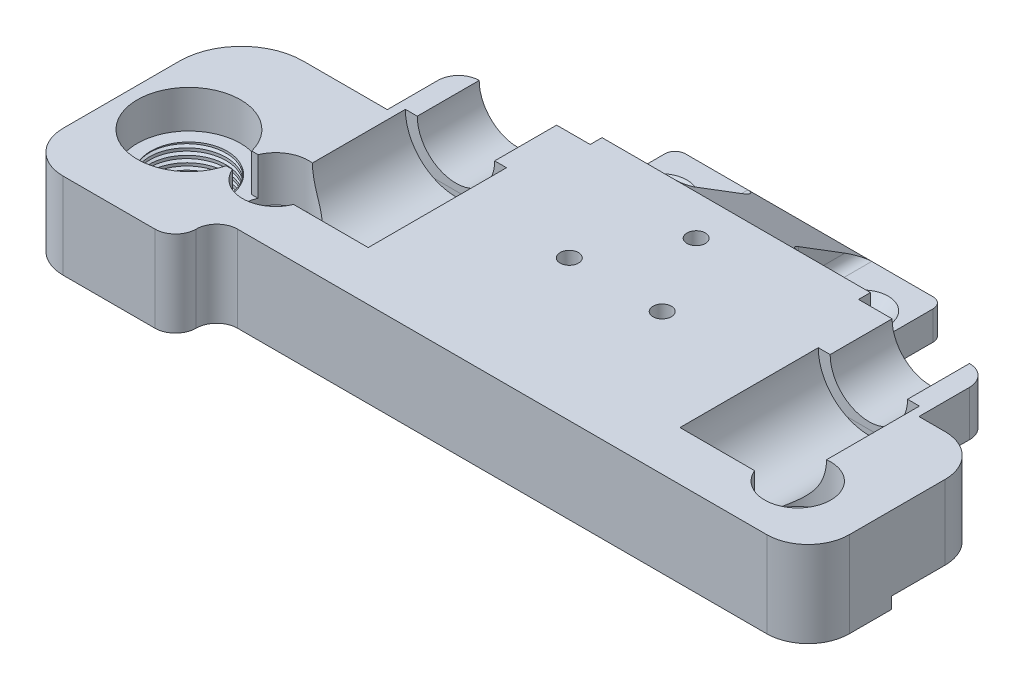
SolidWorks part; units mm, degrees
material "ABS"
ref_plane "Front Plane" through (0, 0, 0) normal (0, 0, 1) x (1, 0, 0)
ref_plane "Top Plane" through (0, 0, 0) normal (0, 1, 0) x (1, 0, 0)
ref_plane "Right Plane" through (0, 0, 0) normal (1, 0, 0) x (0, 0, -1)
sketch "Sketch1" plane through (0, 0, 0) normal (0, 1, 0) x (1, 0, 0)
  line L0 (-0.0671, 38.0105) -> (-0.0671, -29.1298) construction
  line L1 (16.4429, 34.3516) -> (-16.5771, 34.3516)
  line L2 (-41.0754, 15.1359) -> (-16.5771, 15.1359)
  line L3 (-16.5771, 15.1359) -> (-16.5771, 34.3516)
  line L4 (-41.0754, 15.1359) -> (-41.0754, -6.8091)
  line L5 (40.9412, 15.1359) -> (40.9412, -6.8091)
  line L6 (40.9412, 15.1359) -> (16.4429, 15.1359)
  line L7 (16.4429, 15.1359) -> (16.4429, 34.3516)
  line L10 (-41.0754, -6.8091) -> (40.9412, -6.8091)
  circle A0 centre (-12.4496, 28.5096) radius 1.4224
  circle A2 centre (-32.1854, 0.8109) radius 1.9304
  circle A3 centre (32.0512, 0.8109) radius 1.9304
  circle A5 centre (12.3154, 28.5096) radius 1.4224
  point P17 (-0.0671, 34.3516)
  point P20 (-16.5771, 34.3516)
  dimension "D1" = 2.8448
  dimension "D2" = 33.02
  dimension "D3" = 3.8608
  dimension "D6" = 34.0106
  dimension "D7" = 24.765
  dimension "D8" = 64.2366
  dimension "D12" = 5.842
  dimension "D13" = 8.89
  dimension "D14" = 7.62
extrude "Boss-Extrude1" add sketch "Sketch1" along normal blind 3.556
sketch "Sketch3" plane through (0, 0, 0) normal (0, -1, 0) x (1, 0, 0)
  line L0 (40.9412, 6.8091) -> (40.9412, -15.1359) construction
  line L1 (-41.0754, 6.8091) -> (40.9412, 6.8091)
  line L2 (-41.0754, 6.8091) -> (-41.0754, -3.4667)
  line L3 (-41.0754, -3.4667) -> (40.9412, -3.4667)
  line L4 (40.9412, 6.8091) -> (40.9412, -3.4667)
  circle A0 centre (32.0512, -0.8109) radius 1.9304
  circle A1 centre (-32.1854, -0.8109) radius 1.9304
  dimension "D2" = 3.8608
  dimension "D3" = 3.8608
extrude "Boss-Extrude2" add sketch "Sketch3" along normal blind 1.9304
hole_wizard "CSK for M4 Flat Head Machine Screw1" positions "Sketch19" profile "Sketch18" countersink size "M4" standard "ANSI Metric" end condition through all
sketch "Sketch19" plane through (0, 3.556, 0) normal (0, 1, 0) x (1, 0, 0)
  point P0 (-32.1854, 0.8109)
  point P3 (32.0512, 0.8109)
sketch "Sketch18" plane through (-32.1854, 3.556, -0.8109) normal (1, 0, 0) x (0, 0, 1)
  line L0 (0, 0) -> (0, 5.4864)
  line L1 (0, 5.4864) -> (2.25, 5.4864)
  line L2 (2.25, 5.4864) -> (2.25, 1.814)
  line L3 (2.25, 1.814) -> (4.064, 0)
  line L5 (4.064, 0) -> (0, 0)
  line L6 (-2.25, 1.814) -> (-4.064, 0) construction
  line L11 (0, -6.35) -> (0, 107.95) construction
  dimension "Thru Hole Dia." = 4.5
  dimension "Thru Hole Depth" = 5.4864
  dimension "Near C'Sink Dia." = 8.128
  dimension "Near C'Sink Angle" = 90
hole_wizard "CSK for M3 Flat Head Machine Screw2" positions "Sketch22" profile "Sketch21" countersink size "M3" standard "ANSI Metric" end condition through all
sketch "Sketch22" plane through (0, 3.556, 0) normal (0, 1, 0) x (1, 0, 0)
  point P0 (-12.4496, 28.5096)
  point P3 (12.3154, 28.5096)
sketch "Sketch21" plane through (-12.4496, 3.556, -28.5096) normal (1, 0, 0) x (0, 0, 1)
  line L0 (0, 0) -> (0, 5.4864)
  line L1 (0, 5.4864) -> (1.7, 5.4864)
  line L2 (1.7, 5.4864) -> (1.7, 1.45)
  line L3 (1.7, 1.45) -> (3.15, 0)
  line L5 (3.15, 0) -> (0, 0)
  line L6 (-1.7, 1.45) -> (-3.15, 0) construction
  line L11 (0, -6.35) -> (0, 107.95) construction
  dimension "Thru Hole Dia." = 3.4
  dimension "Thru Hole Depth" = 5.4864
  dimension "Near C'Sink Dia." = 6.3
  dimension "Near C'Sink Angle" = 90
sketch "Sketch24" plane through (0, 3.556, 0) normal (0, 1, 0) x (1, 0, 0)
  line L0 (-32.7696, 23.8995) -> (-16.5771, 23.8995)
  line L1 (-16.5771, 25.3596) -> (16.4429, 25.3596)
  line L2 (16.4429, 15.1359) -> (16.4429, 34.3516) construction
  line L3 (-16.5771, 34.3516) -> (-16.5771, 15.1359) construction
  line L4 (-32.7696, 23.8995) -> (-32.7696, 5.6115)
  line L5 (-32.7696, 5.6115) -> (32.6354, 5.6115)
  line L6 (32.6354, 5.6115) -> (32.6354, 23.8995)
  line L7 (32.6354, 23.8995) -> (16.4429, 23.8995)
  line L9 (16.4429, 23.8995) -> (16.4429, 25.3596)
  line L10 (-16.5771, 23.8995) -> (-16.5771, 25.3596)
  circle A1 centre (-12.4496, 28.5096) radius 3.15 construction
  dimension "D3" = 19.7481
  dimension "D4" = 18.288
  dimension "D1" = 65.405
  dimension "D2" = 18.288
extrude "Boss-Extrude3" add sketch "Sketch24" along normal blind 6.2738
sketch "Sketch26" plane through (0, 0, -5.6115) normal (0, 0, 1) x (1, 0, 0)
  line L0 (-32.7696, 3.556) -> (32.6354, 3.556) construction
  line L3 (32.6354, 9.8298) -> (32.6354, 3.556) construction
  circle A0 centre (-25.4671, 9.144) radius 4.7625
  circle A1 centre (25.3329, 9.144) radius 4.7625
  point P0 (-25.4671, 9.144)
  point P1 (25.3329, 9.144)
  dimension "D5" = 9.525
  dimension "D6" = 9.525
  dimension "D1" = 50.8
  dimension "D2" = 7.3025
  dimension "D3" = 5.588
  dimension "D4" = 5.588
extrude "Cut-Extrude1" cut sketch "Sketch26" against normal through all
sketch "Sketch28" plane through (0, 0, -5.6115) normal (0, 0, 1) x (1, 0, 0)
  circle A0 centre (25.3329, 9.144) radius 6.223
  circle A1 centre (-25.4671, 9.144) radius 6.223
  arc A5 (-30.18, 9.8298) -> (-20.7542, 9.8298) centre (-25.4671, 9.144) ccw construction
  arc A7 (20.62, 9.8298) -> (30.0458, 9.8298) centre (25.3329, 9.144) ccw construction
  dimension "D1" = 12.446
extrude "Cut-Extrude2" cut sketch "Sketch28" against normal blind 10.668
sketch "Sketch29" plane through (0, 9.8298, 0) normal (0, 1, 0) x (1, 0, 0)
  line L0 (-0.0671, 20.4349) -> (-0.0671, 25.3596) construction
  line L3 (12.3154, 25.3596) -> (-12.4496, 25.3596) construction
  line L4 (-0.0671, 20.4349) -> (-5.7821, 10.5362)
  line L5 (-5.7821, 10.5362) -> (5.6479, 10.5362)
  line L6 (5.6479, 10.5362) -> (-0.0671, 20.4349)
  line L7 (-0.0671, 10.5362) -> (-0.0671, 5.6115) construction
  line L8 (-19.282, 5.6115) -> (19.1478, 5.6115) construction
  circle A0 centre (-0.0671, 13.8358) radius 3.2996 construction
  dimension "D1" = 11.43
ref_plane "Plane1" through (0, 11.0998, 0) normal (0, 1, 0) x (1, 0, 0)
ref_plane "Plane3" through (0, 0, -10.5362) normal (0, 0, -1) x (-1, 0, 0)
ref_plane "Plane4" through (0, 0, -20.4349) normal (0, 0, -1) x (-1, 0, 0)
sketch "Sketch40" plane through (0, 3.556, 0) normal (0, 1, 0) x (1, 0, 0)
  line L0 (-32.7696, 15.1359) -> (-41.0754, 15.1359)
  line L1 (-41.0754, 15.1359) -> (-41.0754, -6.8091)
  line L2 (-41.0754, -6.8091) -> (40.9412, -6.8091)
  line L3 (40.9412, -6.8091) -> (40.9412, 15.1359)
  line L4 (40.9412, 15.1359) -> (32.6354, 15.1359)
  line L6 (32.6354, 15.1359) -> (32.6354, 5.6115)
  line L7 (32.6354, 5.6115) -> (-32.7696, 5.6115)
  line L8 (-32.7696, 5.6115) -> (-32.7696, 15.1359)
  circle A0 centre (-32.1854, 0.8109) radius 4.064
  circle A1 centre (32.0512, 0.8109) radius 4.064
extrude "Boss-Extrude5" add sketch "Sketch40" along normal blind 6.2738
sketch "Sketch54" plane through (0, 9.8298, 0) normal (0, 1, 0) x (1, 0, 0)
  line L0 (0, -22.7441) -> (0, 38.7133) construction
  line L1 (-41.0754, 15.1359) -> (-36.59, 15.1359)
  line L4 (-41.0754, -6.8091) -> (40.9412, -6.8091) construction
  line L5 (-32.7696, 15.1359) -> (-41.0754, 15.1359) construction
  line L6 (-41.0754, 3.4667) -> (-41.0754, -6.8091)
  line L7 (-41.0754, 15.1359) -> (-50.7274, 15.1359)
  line L8 (-50.7274, 15.1359) -> (-50.7274, -6.8091)
  line L9 (-41.0754, 15.1359) -> (-41.0754, -6.8091) construction
  line L10 (-50.7274, -6.8091) -> (-50.7274, -11.8891)
  line L11 (-50.7274, -11.8891) -> (-31.8009, -11.8891)
  line L12 (-31.8009, -11.8891) -> (-31.8009, -6.8091)
  line L13 (-31.8009, -6.8091) -> (-41.0754, -6.8091)
  line L14 (-36.59, 15.1359) -> (-36.59, 3.4667)
  line L15 (-36.59, 3.4667) -> (-41.0754, 3.4667)
  line L16 (-41.0754, 3.4667) -> (40.9412, 3.4667) construction
  dimension "D1" = 9.652
  dimension "D3" = 5.08
extrude "Boss-Extrude6" add sketch "Sketch54" against normal up to vertex (11.7602 mm away) up to point (40.9412, -1.9304, 6.8091)
sketch "Sketch42" plane through (0, 0, -5.6115) normal (0, 0, -1) x (-1, 0, 0)
  line L2 (-31.518, 9.8298) -> (-19.1478, 9.8298)
  line L3 (19.282, 9.8298) -> (31.6522, 9.8298)
  arc A0 (-31.518, 9.8298) -> (-19.1478, 9.8298) centre (-25.3329, 9.144) ccw
  arc A1 (-31.518, 9.8298) -> (-19.1478, 9.8298) centre (-25.3329, 9.144) ccw construction
  arc A2 (31.6522, 9.8298) -> (19.282, 9.8298) centre (25.4671, 9.144) cw
  arc A3 (19.282, 9.8298) -> (31.6522, 9.8298) centre (25.4671, 9.144) ccw construction
  dimension "D1" = 6.223
extrude "Cut-Extrude4" cut sketch "Sketch42" against normal blind 6.35
ref_plane "Plane5" through (0, 0, -5.6115) normal (0, 0, 1) x (1, 0, 0)
sketch "Sketch43" plane through (0, 9.8298, 0) normal (0, 1, 0) x (1, 0, 0)
  line L0 (-38.226, 0.8109) -> (-16.2684, 0.8109) construction
  line L1 (0, -22.6141) -> (0, 48.9637) construction
  circle A0 centre (-32.1854, 0.8109) radius 7.62
  circle A2 centre (-42.8534, 0.8109) radius 3.048
  circle A3 centre (-42.8534, 0.8109) radius 4.699
  point P19 (0, 48.9637)
  dimension "D1" = 15.24
  dimension "D3" = 6.096
  dimension "D4" = 9.398
  dimension "D2" = 0
extrude "Cut-Extrude10" cut sketch "Sketch43" against normal through all contours A3 A2 | A2 | A3 region at (-39.0202, 9.8298, -0.8109) region at (-42.8534, 9.8298, -0.8109) region at (-39.7772, 9.8298, -2.3471)
sketch "Sketch55" plane through (0, 9.8298, 0) normal (0, 1, 0) x (1, 0, 0)
  line L0 (0, -23.4742) -> (0, 45.6426) construction
  circle A0 centre (-42.8534, 0.8109) radius 6.35
  dimension "D1" = 12.7
extrude "Cut-Extrude11" cut sketch "Sketch55" against normal blind 5.334
ref_plane "Plane7" through (0, 5.7658, 0) normal (0, 1, 0) x (1, 0, 0)
sketch "Sketch56" plane through (0, 5.7658, 0) normal (0, 1, 0) x (1, 0, 0)
  circle A0 centre (-42.8534, 0.8109) radius 4.699
  dimension "D1" = 9.398
curve "Helix/Spiral4" pitch 0.7937 height 10.16 radius 4.699 centre (-42.8534, 5.7658, -0.8109) axis (0, -1, 0) start towards (0, 0, 1)
ref_plane "Plane8" through (-42.8534, 0, 0) normal (-1, 0, 0) x (0, 0, 1)
sketch "Sketch58" plane through (-42.8534, 0, 0) normal (-1, 0, 0) x (0, 0, 1)
  line L0 (3.8878, 3.3595) -> (3.8878, 8.8917) construction
  line L2 (3.7608, 7.2661) -> (4.2688, 7.5594)
  line L3 (4.2688, 7.5594) -> (3.7608, 7.8527)
  line L4 (3.7608, 7.8527) -> (3.7608, 7.2661)
  circle A0 centre (3.9301, 7.5594) radius 0.1693 construction
  spline S0 degree 3 poles (3.8881, 5.7658) (3.8881, 5.7493) (3.6415, 5.7159) (2.5885, 5.6662) (1.0139, 5.6164) (-0.8406, 5.5666) (-2.6906, 5.5168) (-4.2521, 5.467) (-5.2858, 5.4172) (-5.6328, 5.3674) (-5.2401, 5.3176) (-4.1679, 5.2678) (-2.5806, 5.218) (-0.7218, 5.1682) (1.1233, 5.1183) (2.6717, 5.0685) (3.6858, 5.0187) (4.01, 4.9689) (3.5945, 4.9191) (2.5032, 4.8693) (0.9034, 4.8195) (-0.9594, 4.7697) (-2.7994, 4.7199) (-4.3343, 4.6701) (-5.3287, 4.6203) (-5.6299, 4.5705) (-5.1918, 4.5207) (-4.0816, 4.4709) (-2.4695, 4.4211) (-0.603, 4.3713) (1.2316, 4.3215) (2.7528, 4.2717) (3.7273, 4.2219) (4.0056, 4.1721) (3.5448, 4.1223) (2.4159, 4.0725) (0.7918, 4.0227) (-1.0781, 3.9729) (-2.907, 3.9231) (-4.4144, 3.8733) (-5.3689, 3.8234) (-5.6241, 3.7736) (-5.1408, 3.7238) (-3.9933, 3.674) (-2.3575, 3.6242) (-0.4844, 3.5744) (1.3386, 3.5246) (2.8318, 3.4748) (3.7661, 3.425) (3.9982, 3.3752) (3.4925, 3.3254) (2.3266, 3.2756) (0.6793, 3.2258) (-1.1966, 3.176) (-3.0134, 3.1262) (-4.4922, 3.0764) (-5.4063, 3.0266) (-5.6153, 2.9768) (-5.0872, 2.927) (-3.903, 2.8772) (-2.2445, 2.8274) (-0.3659, 2.7776) (1.4443, 2.7278) (2.9085, 2.678) (3.8021, 2.6282) (3.988, 2.5783) (3.4376, 2.5285) (2.2354, 2.4787) (0.5658, 2.4289) (-1.315, 2.3791) (-3.1184, 2.3293) (-4.5679, 2.2795) (-5.4409, 2.2297) (-5.6036, 2.1799) (-5.031, 2.1301) (-3.8109, 2.0803) (-2.1306, 2.0305) (-0.2478, 1.9807) (1.5486, 1.9309) (2.983, 1.8811) (3.8354, 1.8313) (3.9749, 1.7815) (3.3801, 1.7317) (2.1424, 1.6819) (0.4516, 1.6321) (-1.433, 1.5823) (-3.222, 1.5325) (-4.6412, 1.4827) (-5.4727, 1.4329) (-5.589, 1.3831) (-4.9722, 1.3333) (-3.717, 1.2834) (-2.0159, 1.2336) (-0.13, 1.1838) (1.6515, 1.134) (3.0552, 1.0842) (3.8658, 1.0344) (3.9588, 0.9846) (3.3201, 0.9348) (2.0476, 0.885) (0.3365, 0.8352) (-1.5506, 0.7854) (-3.3242, 0.7356) (-4.7122, 0.6858) (-5.5017, 0.636) (-5.5715, 0.5862) (-4.9109, 0.5364) (-3.6213, 0.4866) (-1.9005, 0.4368) (-0.0125, 0.387) (1.7529, 0.3372) (3.1251, 0.2874) (3.8933, 0.2376) (3.9399, 0.1878) (3.2575, 0.138) (1.951, 0.0882) (0.2208, 0.0383) (-1.6678, -0.0115) (-3.4248, -0.0613) (-4.7809, -0.1111) (-5.5278, -0.1609) (-5.5511, -0.2107) (-4.8471, -0.2605) (-3.5239, -0.3103) (-1.7844, -0.3601) (0.1044, -0.4099) (1.8528, -0.4597) (3.1925, -0.5095) (3.918, -0.5593) (3.918, -0.6091) (3.1925, -0.6589) (1.8528, -0.7087) (0.1044, -0.7585) (-1.7844, -0.8083) (-3.5239, -0.8581) (-4.8471, -0.9079) (-5.5511, -0.9577) (-5.5278, -1.0075) (-4.7809, -1.0573) (-3.4248, -1.1071) (-1.6678, -1.1569) (0.2208, -1.2067) (1.951, -1.2566) (3.2575, -1.3064) (3.9399, -1.3562) (3.8933, -1.406) (3.1251, -1.4558) (1.7529, -1.5056) (-0.0125, -1.5554) (-1.9005, -1.6052) (-3.6213, -1.655) (-4.9109, -1.7048) (-5.5715, -1.7546) (-5.5017, -1.8044) (-4.7122, -1.8542) (-3.3242, -1.904) (-1.5506, -1.9538) (0.3365, -2.0036) (2.0476, -2.0534) (3.3201, -2.1032) (3.9588, -2.153) (3.8658, -2.2028) (3.0552, -2.2526) (1.6515, -2.3024) (-0.13, -2.3522) (-2.0159, -2.402) (-3.717, -2.4518) (-4.9722, -2.5017) (-5.589, -2.5515) (-5.4727, -2.6013) (-4.6412, -2.6511) (-3.222, -2.7009) (-1.433, -2.7507) (0.4516, -2.8005) (2.1424, -2.8503) (3.3801, -2.9001) (3.9749, -2.9499) (3.8354, -2.9997) (2.983, -3.0495) (1.5486, -3.0993) (-0.2478, -3.1491) (-2.1306, -3.1989) (-3.8109, -3.2487) (-5.031, -3.2985) (-5.6036, -3.3483) (-5.4409, -3.3981) (-4.5679, -3.4479) (-3.1184, -3.4977) (-1.315, -3.5475) (0.5658, -3.5973) (2.2354, -3.6471) (3.4376, -3.6969) (3.988, -3.7467) (3.8021, -3.7966) (2.9085, -3.8464) (1.4443, -3.8962) (-0.3659, -3.946) (-2.2445, -3.9958) (-3.903, -4.0456) (-5.0872, -4.0954) (-5.6153, -4.1452) (-5.4062, -4.195) (-4.4924, -4.2448) (-3.0129, -4.2946) (-1.1984, -4.3443) (0.0577, -4.3777) (0.6412, -4.3942) knots 0 0 0 0 0.004902 0.009804 0.014706 0.019608 0.02451 0.029412 0.034314 0.039216 0.044118 0.04902 0.053922 0.058824 0.063725 0.068627 0.073529 0.078431 0.083333 0.088235 0.093137 0.098039 0.102941 0.107843 0.112745 0.117647 0.122549 0.127451 0.132353 0.137255 0.142157 0.147059 0.151961 0.156863 0.161765 0.166667 0.171569 0.176471 0.181373 0.186275 0.191176 0.196078 0.20098 0.205882 0.210784 0.215686 0.220588 0.22549 0.230392 0.235294 0.240196 0.245098 0.25 0.254902 0.259804 0.264706 0.269608 0.27451 0.279412 0.284314 0.289216 0.294118 0.29902 0.303922 0.308824 0.313725 0.318627 0.323529 0.328431 0.333333 0.338235 0.343137 0.348039 0.352941 0.357843 0.362745 0.367647 0.372549 0.377451 0.382353 0.387255 0.392157 0.397059 0.401961 0.406863 0.411765 0.416667 0.421569 0.426471 0.431373 0.436275 0.441176 0.446078 0.45098 0.455882 0.460784 0.465686 0.470588 0.47549 0.480392 0.485294 0.490196 0.495098 0.5 0.504902 0.509804 0.514706 0.519608 0.52451 0.529412 0.534314 0.539216 0.544118 0.54902 0.553922 0.558824 0.563725 0.568627 0.573529 0.578431 0.583333 0.588235 0.593137 0.598039 0.602941 0.607843 0.612745 0.617647 0.622549 0.627451 0.632353 0.637255 0.642157 0.647059 0.651961 0.656863 0.661765 0.666667 0.671569 0.676471 0.681373 0.686275 0.691176 0.696078 0.70098 0.705882 0.710784 0.715686 0.720588 0.72549 0.730392 0.735294 0.740196 0.745098 0.75 0.754902 0.759804 0.764706 0.769608 0.77451 0.779412 0.784314 0.789216 0.794118 0.79902 0.803922 0.808824 0.813725 0.818627 0.823529 0.828431 0.833333 0.838235 0.843137 0.848039 0.852941 0.857843 0.862745 0.867647 0.872549 0.877451 0.882353 0.887255 0.892157 0.897059 0.901961 0.906863 0.911765 0.916667 0.921569 0.926471 0.931373 0.936275 0.941176 0.946078 0.95098 0.955882 0.960784 0.965686 0.970588 0.97549 0.980392 0.985294 0.990196 0.995098 1 1 1 1 construction
  dimension "D1" = 0.508
  dimension "D2" = 0.127
sweep "Cut-Sweep9" cut profiles "Sketch58" path "Helix/Spiral4" align with end faces yes
fillet "Fillet1" radius 5.08 3 edges at (40.9412, 4.9149, -15.1359) (40.9412, 3.9497, 6.8091) (-50.7274, 3.9497, 11.8891)
fillet "Fillet2" radius 2.54 2 edges at (-32.7696, 6.6929, -23.8995) (32.6354, 6.6929, -23.8995)
fillet "Fillet3" radius 1.27 2 edges at (-16.5771, 1.778, -34.3516) (16.4429, 1.778, -34.3516)
sketch "Sketch63" plane through (32.6354, 0, 0) normal (1, 0, 0) x (0, 0, -1)
  line L0 (15.1359, 0) -> (15.1359, 3.556)
  line L1 (15.1359, 3.556) -> (17.6759, 3.556)
  line L2 (15.1359, 3.556) -> (23.8995, 3.556) construction
  line L3 (17.6759, 3.556) -> (15.1359, 0)
  dimension "D1" = 2.54
extrude "Boss-Extrude8" add sketch "Sketch63" against normal blind 65.405
sketch "Sketch65" plane through (0, 0, -15.1359) normal (0, 0, 1) x (1, 0, 0)
  line L0 (-28.2057, 3.556) -> (-22.7285, 3.556)
  line L1 (22.5943, 3.556) -> (28.0715, 3.556)
  arc A0 (-28.2057, 3.556) -> (-22.7285, 3.556) centre (-25.4671, 9.144) ccw
  arc A1 (22.5943, 3.556) -> (28.0715, 3.556) centre (25.3329, 9.144) ccw
extrude "Cut-Extrude14" cut sketch "Sketch65" against normal blind 1.1436
hole_wizard "#4-40 Tapped Hole2" positions "Sketch70" profile "Sketch69" tap size "#4-40" standard "ANSI Inch" end condition through all
sketch "Sketch70" plane through (0, 9.8298, 0) normal (0, 1, 0) x (1, 0, 0)
  point P0 (5.6479, 10.5362)
  point P3 (-0.0671, 20.4349)
  point P6 (-5.7821, 10.5362)
sketch "Sketch69" plane through (5.6479, 9.8298, -10.5362) normal (1, 0, 0) x (0, 0, 1)
  line L0 (0, 0) -> (0, 12.0191)
  line L1 (0, 12.0191) -> (1.1303, 12.0191)
  line L2 (1.1303, 12.0191) -> (1.1303, 0)
  line L5 (1.1303, 0) -> (0, 0)
  line L11 (0, -6.35) -> (0, 107.95) construction
  dimension "Thru Tap Drill Dia." = 2.2606
  dimension "Thru Tap Drill Depth" = 12.0191
cosmetic thread "Hole Thread1" parameters "D2"=2.8448
cosmetic thread "Hole Thread2" parameters "D2"=2.8448
cosmetic thread "Hole Thread3" parameters "D2"=2.8448
sketch "Sketch73" plane through (0, 0, -25.3596) normal (0, 0, -1) x (-1, 0, 0)
  line L1 (-40.9412, 9.8298) -> (50.7274, 9.8298)
  line L2 (-40.9412, 9.8298) -> (-40.9412, 9.4869)
  line L3 (-40.9412, 9.4869) -> (50.7274, 9.4869)
  line L4 (50.7274, 9.8298) -> (50.7274, 9.4869)
  line L5 (50.7274, -1.9304) -> (50.7274, 9.8298) construction
  dimension "D1" = 0.3429
extrude "Cut-Extrude17" cut sketch "Sketch73" against normal through all
fillet "Fillet6" radius 2.54 2 edges at (-31.8009, 3.7782, 11.8891) (-31.8009, 3.7782, 6.8091)
sketch "Sketch79" plane through (0, -1.9304, 0) normal (0, -1, 0) x (1, 0, 0)
  line L0 (-49.1168, -3.4667) -> (-50.7274, -3.4667)
  line L1 (-50.7274, -15.1359) -> (-50.7274, 6.8091) construction
  line L2 (-36.59, -3.4667) -> (40.9412, -3.4667) construction
  line L3 (-50.7274, -3.4667) -> (-50.7274, -15.1359)
  line L4 (-50.7274, -15.1359) -> (-36.59, -15.1359)
  line L5 (-36.59, -15.1359) -> (-36.59, -3.4667)
  arc A0 (-36.59, -3.4667) -> (-49.1168, -3.4667) centre (-42.8534, -0.8109) cw
extrude "Cut-Extrude21" cut sketch "Sketch79" against normal up to surface (1.9304 mm away) up to face at (5.6479, 0, -9.4059)
sketch "Sketch80" plane through (0, 9.4869, 0) normal (0, 1, 0) x (1, 0, 0)
  line L0 (-36.7013, -0.7622) -> (-35.9326, -0.7622)
  line L1 (-36.7013, 2.3839) -> (-35.9326, 2.3839)
  circle A2 centre (-42.8534, 0.8109) radius 6.35 construction
  arc A3 (-31.6807, 4.8434) -> (-28.4283, -0.7385) centre (-32.1854, 0.8109) ccw construction
  circle A4 centre (-32.1854, 0.8109) radius 4.064 construction
  arc A5 (-36.7013, 2.3839) -> (-36.7013, -0.7622) centre (-42.8534, 0.8109) cw
  arc A6 (-35.9326, -0.7622) -> (-35.9326, 2.3839) centre (-32.1854, 0.8109) cw
extrude "Cut-Extrude22" cut sketch "Sketch80" against normal up to surface (4.9911 mm away) up to face at (-42.1515, 4.4958, -0.0269)
fillet "Fillet7" radius 7.62 1 edges at (-50.7274, 4.7435, -15.1359)
sketch "Sketch83" plane through (40.9412, 0, 0) normal (1, 0, 0) x (0, 0, -1)
  line L0 (-11.8891, -1.9304) -> (7.6141, -1.9304)
  line L1 (7.6141, -1.9304) -> (7.6141, -1.4224)
  line L2 (7.6141, -1.9304) -> (7.6141, 0) construction
  line L3 (7.6141, -1.4224) -> (-11.8891, -1.4224)
  line L5 (-11.8891, -1.4224) -> (-11.8891, -1.9304)
  line L6 (-11.8891, -1.9304) -> (-11.8891, 9.4869) construction
  dimension "D1" = 0.508
extrude "Cut-Extrude23" cut sketch "Sketch83" against normal through all
sketch "Sketch85" plane through (0, 0, -23.8995) normal (0, 0, -1) x (-1, 0, 0)
  line L0 (50.7274, 9.4869) -> (50.7274, 0) construction
  line L1 (-40.9412, 9.4869) -> (50.7274, 9.4869)
  line L2 (-40.9412, 9.4869) -> (-40.9412, 9.144)
  line L3 (-40.9412, 9.144) -> (50.7274, 9.144)
  line L4 (50.7274, 9.4869) -> (50.7274, 9.144)
  arc A0 (-25.3329, 4.3815) -> (-20.5704, 9.144) centre (-25.3329, 9.144) ccw
  arc A1 (-30.0954, 9.144) -> (-20.5828, 9.4869) centre (-25.3329, 9.144) ccw construction
  line M2 (-16.4429, 3.556) -> (-16.4429, 9.4869)
  line M3 (-16.4429, 9.4869) -> (-20.5828, 9.4869)
  arc M4 (-20.5828, 9.4869) -> (-30.0954, 9.144) centre (-25.3329, 9.144) cw
extrude "Cut-Extrude24" cut sketch "Sketch85" against normal mid plane 101.6 contours L4 L1 L3 M2 | L3 M4 M2 M3 | L2 L3 L1 M4 region at (30.7579, 9.3154, -23.8995) region at (18.5087, 9.3155, -23.8995) region at (-17.1423, 9.3155, -23.8995)
sketch "Sketch86" plane through (0, 0, 0) normal (1, 0, 0) x (0, 0, -1)
  line L0 (25.3596, 9.144) -> (34.3516, 3.556)
  line L1 (34.3516, 3.556) -> (25.3596, 3.556)
  line L2 (25.3596, 3.556) -> (25.3596, 9.144)
extrude "Boss-Extrude10" add sketch "Sketch86" along normal mid plane 12.7
fillet "Fillet9" radius 1.27 4 edges at (-6.35, 3.556, -29.8556) (-6.35, 6.35, -25.3596) (6.35, 3.556, -29.8556) (6.35, 6.35, -25.3596)
